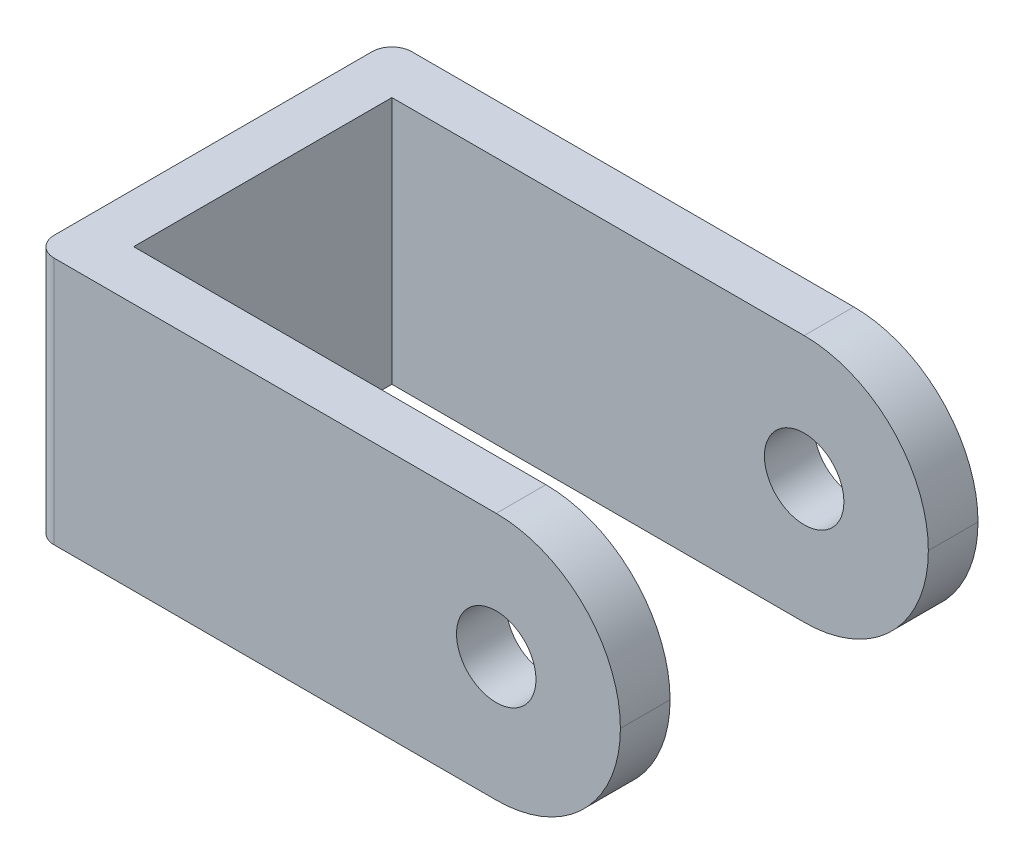
SolidWorks part; units mm, degrees
ref_plane "Спереди" through (0, 0, 0) normal (0, 0, 1) x (1, 0, 0)
ref_plane "Сверху" through (0, 0, 0) normal (0, 1, 0) x (1, 0, 0)
ref_plane "Справа" through (0, 0, 0) normal (1, 0, 0) x (0, 0, -1)
sketch "Эскиз1" plane through (0, 0, 0) normal (0, 1, 0) x (1, 0, 0)
  line L0 (0, 16) -> (0, -16)
  line L1 (2, -18) -> (59, -18)
  line L2 (59, -18) -> (59, -13)
  line L3 (59, -13) -> (5, -13)
  line L4 (5, -13) -> (5, 13)
  line L5 (5, 13) -> (59, 13)
  line L6 (59, 13) -> (59, 18)
  line L7 (59, 18) -> (2, 18)
  arc A0 (2, -18) -> (0, -16) centre (2, -16) cw
  arc A1 (0, 16) -> (2, 18) centre (2, 16) cw
  point P11 (0, -18)
  point P14 (0, 18)
  dimension "D6" = 2
  dimension "D1" = 59
  dimension "D2" = 5
  dimension "D3" = 5
  dimension "D4" = 36
  dimension "D5" = 18
extrude "Бобышка-Вытянуть1" add sketch "Эскиз1" along normal blind 25
fillet "Скругление1" radius 12.5 4 edges at (59, 25, -15.5) (59, 0, -15.5) (59, 0, 15.5) (59, 25, 15.5)
sketch "Эскиз2" plane through (0, 0, 18) normal (0, 0, 1) x (1, 0, 0)
  circle A0 centre (46.5, 12.5) radius 4
  dimension "D1" = 8
extrude "Вырез-Вытянуть1" cut sketch "Эскиз2" against normal through all
